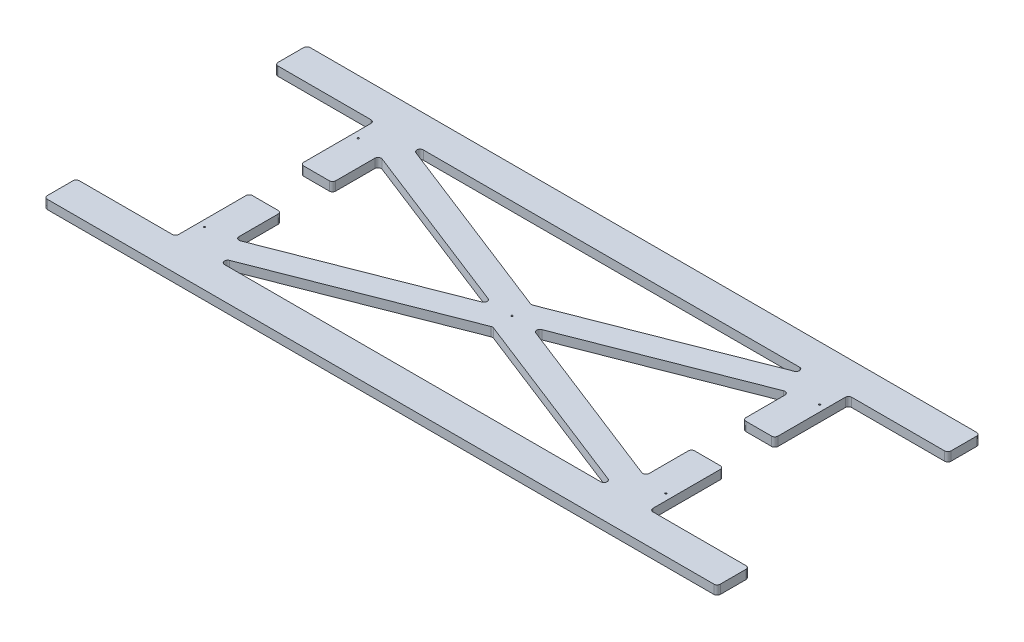
SolidWorks part; units mm, degrees
ref_plane "Front Plane" through (0, 0, 0) normal (0, 0, 1) x (1, 0, 0)
ref_plane "Top Plane" through (0, 0, 0) normal (0, 1, 0) x (1, 0, 0)
ref_plane "Right Plane" through (0, 0, 0) normal (1, 0, 0) x (0, 0, -1)
sketch "Sketch1" plane through (0, 0, 0) normal (0, 1, 0) x (1, 0, 0)
  line L1 (-666.75, 260.35) -> (666.75, 260.35)
  line L2 (-666.75, 260.35) -> (-666.75, -260.35)
  line L3 (-666.75, -260.35) -> (666.75, -260.35)
  line L4 (666.75, 260.35) -> (666.75, -260.35)
  line L5 (-666.75, 260.35) -> (666.75, -260.35) construction
  line L6 (-666.75, -260.35) -> (666.75, 260.35) construction
  point P0 (0, 0)
  dimension "D1" = 520.7
  dimension "D2" = 1333.5
extrude "Boss-Extrude1" add sketch "Sketch1" along normal blind 17.78
fillet "Fillet1" radius 6.35 4 edges at (-666.75, 8.89, 260.35) (-666.75, 8.89, -260.35) (666.75, 8.89, -260.35) (666.75, 8.89, 260.35)
hole_wizard "1/8 (0.125) Diameter Hole1" positions "Sketch3" profile "Sketch4" hole size "1/8" standard "ANSI Inch" end condition through all
sketch "Sketch3" plane through (0, 17.78, 0) normal (0, 1, 0) x (1, 0, 0)
  line L1 (-457.2, -152.4) -> (457.2, -152.4) construction
  line L2 (-457.2, -152.4) -> (-457.2, 152.4) construction
  line L3 (-457.2, 152.4) -> (457.2, 152.4) construction
  line L4 (457.2, -152.4) -> (457.2, 152.4) construction
  line L5 (-457.2, -152.4) -> (457.2, 152.4) construction
  line L6 (-457.2, 152.4) -> (457.2, -152.4) construction
  point P0 (0, 0)
  point P1 (457.2, 152.4)
  point P32 (-457.2, -152.4)
  point P33 (-457.2, 152.4)
  point P34 (457.2, -152.4)
  dimension "D1" = 914.4
  dimension "D2" = 304.8
sketch "Sketch4" plane through (0, 17.78, 0) normal (1, 0, 0) x (0, 0, 1)
  line L0 (0, 0) -> (0, 17.78)
  line L1 (0, 17.78) -> (1.5875, 17.78)
  line L2 (1.5875, 17.78) -> (1.5875, 0)
  line L5 (1.5875, 0) -> (0, 0)
  line L11 (0, -6.35) -> (0, 107.95) construction
  dimension "Thru Hole Dia." = 3.175
  dimension "Thru Hole Depth" = 17.78
sketch "Sketch2" plane through (0, 17.78, 0) normal (0, 1, 0) x (1, 0, 0)
  line L1 (-635, -330.2) -> (635, -330.2)
  line L2 (-635, -330.2) -> (-635, 330.2)
  line L3 (-635, 330.2) -> (635, 330.2)
  line L4 (635, -330.2) -> (635, 330.2)
  line L5 (-635, -330.2) -> (635, 330.2) construction
  line L6 (-635, 330.2) -> (635, -330.2) construction
  point P0 (0, 0)
  dimension "D1" = 660.4
  dimension "D2" = 1270
extrude "Boss-Extrude2" [suppressed] add sketch "Sketch2" along normal blind 9.525
sketch "Sketch5" plane through (0, 17.78, 0) normal (0, 1, 0) x (1, 0, 0)
  line L0 (-406.4, 196.85) -> (406.4, 196.85)
  line L1 (660.4, 260.35) -> (-660.4, 260.35) construction
  line L2 (0, 38.1) -> (-406.4, 196.85)
  line L3 (406.4, 196.85) -> (0, 38.1)
  line L4 (0, 260.35) -> (0, -260.35) construction
  line L5 (-660.4, -260.35) -> (660.4, -260.35) construction
  line L6 (-666.75, 0) -> (666.75, 0) construction
  line L7 (-666.75, 254) -> (-666.75, -254) construction
  line L8 (666.75, -254) -> (666.75, 254) construction
  line L9 (0, -38.1) -> (-406.4, -196.85)
  line L10 (-406.4, -196.85) -> (406.4, -196.85)
  line L11 (406.4, -196.85) -> (0, -38.1)
  line L12 (406.4, 143.8672) -> (406.4, -143.8672)
  line L13 (406.4, -143.8672) -> (38.1, 0)
  line L14 (406.4, 143.8672) -> (38.1, 0)
  line L15 (-406.4, 143.8672) -> (-38.1, 0)
  line L16 (-406.4, 143.8672) -> (-406.4, -143.8672)
  line L17 (-406.4, -143.8672) -> (-38.1, 0)
  line L18 (622.3, -196.85) -> (469.9, -196.85)
  line L19 (-622.3, -196.85) -> (-469.9, -196.85)
  line L20 (-622.3, -196.85) -> (-622.3, 196.85)
  line L21 (-622.3, 196.85) -> (-469.9, 196.85)
  line L22 (-469.9, -196.85) -> (-469.9, 196.85)
  line L23 (-622.3, -196.85) -> (-469.9, 196.85) construction
  line L24 (-622.3, 196.85) -> (-469.9, -196.85) construction
  line L25 (622.3, -196.85) -> (622.3, 196.85)
  line L26 (622.3, 196.85) -> (469.9, 196.85)
  line L27 (469.9, -196.85) -> (469.9, 196.85)
  circle A0 centre (0, 0) radius 38.1 construction
  point P3 (0, 196.85)
  point P30 (-546.1, 0)
  dimension "D2" = 76.2
  dimension "D4" = 152.4
  dimension "D1" = 63.5
  dimension "D3" = 812.8
  dimension "D5" = 44.45
extrude "Cut-Extrude1" cut sketch "Sketch5" against normal through all
fillet "Fillet2" radius 6.35 20 edges at (469.9, 8.89, -196.85) (469.9, 8.89, 196.85) (622.3, 8.89, 196.85) (406.4, 8.89, 143.8672) (406.4, 8.89, 196.85) (622.3, 8.89, -196.85) (406.4, 8.89, -143.8672) (406.4, 8.89, -196.85) (38.1, 8.89, 0) (0, 8.89, 38.1) (0, 8.89, -38.1) (-38.1, 8.89, 0) (-406.4, 8.89, 196.85) (-406.4, 8.89, -196.85) (-406.4, 8.89, -143.8672) (-406.4, 8.89, 143.8672) (-622.3, 8.89, 196.85) (-469.9, 8.89, 196.85) (-469.9, 8.89, -196.85) (-622.3, 8.89, -196.85)
sketch "Sketch6" plane through (0, 17.78, 0) normal (0, 1, 0) x (1, 0, 0)
  line L0 (666.75, -254) -> (666.75, 254) construction
  line L1 (615.95, -196.85) -> (666.75, -196.85)
  line L2 (615.95, -196.85) -> (615.95, 196.85)
  line L3 (615.95, 196.85) -> (666.75, 196.85)
  line L4 (666.75, -196.85) -> (666.75, 196.85)
  line L5 (-666.75, 254) -> (-666.75, -254) construction
  line L6 (-615.95, -196.85) -> (-666.75, -196.85)
  line L7 (-615.95, -196.85) -> (-615.95, 196.85)
  line L8 (-615.95, 196.85) -> (-666.75, 196.85)
  line L9 (-666.75, -196.85) -> (-666.75, 196.85)
  line L10 (-666.75, 0) -> (666.75, 0) construction
  line L11 (-469.9, -190.5) -> (-469.9, 190.5) construction
  line L12 (-469.9, -50.8) -> (-406.4, -50.8)
  line L13 (-469.9, -50.8) -> (-469.9, 50.8)
  line L14 (-469.9, 50.8) -> (-406.4, 50.8)
  line L15 (-406.4, -50.8) -> (-406.4, 50.8)
  line L16 (-469.9, -50.8) -> (-406.4, 50.8) construction
  line L17 (-469.9, 50.8) -> (-406.4, -50.8) construction
  line L18 (406.4, -50.8) -> (469.9, -50.8)
  line L19 (406.4, -50.8) -> (406.4, 50.8)
  line L20 (406.4, 50.8) -> (469.9, 50.8)
  line L21 (469.9, -50.8) -> (469.9, 50.8)
  line L22 (406.4, -50.8) -> (469.9, 50.8) construction
  line L23 (406.4, 50.8) -> (469.9, -50.8) construction
  line L24 (-406.4, 134.5694) -> (-406.4, -134.5694) construction
  line L25 (406.4, -134.5694) -> (406.4, 134.5694) construction
  line L26 (469.9, 190.5) -> (469.9, -190.5) construction
  point P16 (-438.15, 0)
  point P21 (438.15, 0)
  dimension "D1" = 101.6
extrude "Cut-Extrude2" cut sketch "Sketch6" against normal through all
fillet "Fillet3" radius 6.35 12 edges at (-666.75, 8.89, 196.85) (-666.75, 8.89, -196.85) (666.75, 8.89, -196.85) (666.75, 8.89, 196.85) (-406.4, 8.89, 50.8) (-406.4, 8.89, -50.8) (-469.9, 8.89, 50.8) (-469.9, 8.89, -50.8) (469.9, 8.89, -50.8) (406.4, 8.89, -50.8) (469.9, 8.89, 50.8) (406.4, 8.89, 50.8)
